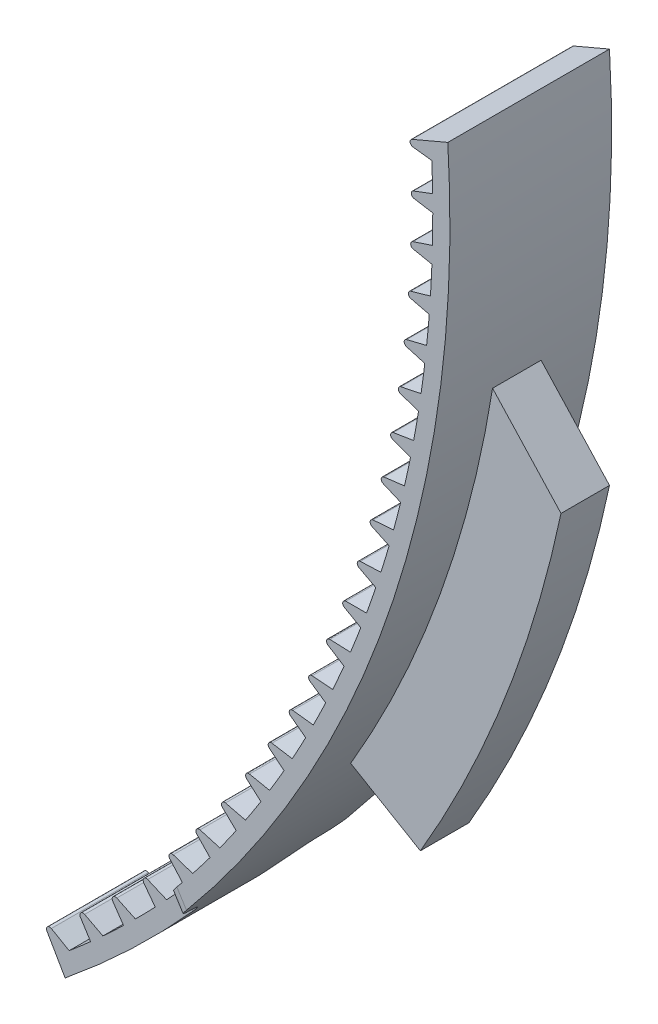
SolidWorks part; units mm, degrees
ref_plane "Plan de face" through (0, 0, 0) normal (0, 0, 1) x (1, 0, 0)
ref_plane "Plan de dessus" through (0, 0, 0) normal (0, 1, 0) x (1, 0, 0)
ref_plane "Plan de droite" through (0, 0, 0) normal (1, 0, 0) x (0, 0, -1)
sketch "Esquisse1" plane through (0, 0, 0) normal (0, 0, 1) x (1, 0, 0)
  line L0 (-30.5715, 0) -> (-35.8869, 0) construction
  line L1 (-30.5715, 0) -> (-32.0715, 2.5981)
  line L2 (-32.0715, 2.5981) -> (-30.323, 1.5885)
  line L3 (-28.998, 2.7351) -> (-30.0249, 4.3591)
  line L4 (-30.0249, 4.3591) -> (-28.2371, 3.4208)
  line L5 (-26.9594, 4.6198) -> (-28.0509, 6.2012)
  line L6 (-28.0509, 6.2012) -> (-26.2268, 5.3356)
  line L7 (-24.9984, 6.5851) -> (-26.1527, 8.1212)
  line L8 (-26.1527, 8.1212) -> (-24.2952, 7.3298)
  line L9 (-23.1181, 8.6277) -> (-24.3333, 10.1161)
  line L10 (-24.3333, 10.1161) -> (-22.4454, 9.4002)
  line L11 (-21.3215, 10.7444) -> (-22.5957, 12.1827)
  line L12 (-22.5957, 12.1827) -> (-20.6805, 11.5433)
  line L13 (-19.6117, 12.9318) -> (-20.9428, 14.3175)
  line L14 (-20.9428, 14.3175) -> (-19.0034, 13.7558)
  line L15 (-17.9913, 15.1861) -> (-19.3771, 16.5172)
  line L16 (-19.3771, 16.5172) -> (-17.4167, 16.034)
  line L17 (-16.463, 17.5039) -> (-17.9013, 18.7781)
  line L18 (-17.9013, 18.7781) -> (-15.923, 18.3742)
  line L19 (-15.0293, 19.8814) -> (-16.5177, 21.0966)
  line L20 (-16.5177, 21.0966) -> (-14.5248, 20.7728)
  line L21 (-13.6925, 22.3147) -> (-15.2286, 23.469)
  line L22 (-15.2286, 23.469) -> (-13.2242, 23.2256)
  line L23 (-12.4547, 24.7998) -> (-14.036, 25.8913)
  line L24 (-14.036, 25.8913) -> (-12.0235, 25.7289)
  line L25 (-11.318, 27.3327) -> (-12.942, 28.3597)
  line L26 (-12.942, 28.3597) -> (-10.9246, 28.2784)
  line L27 (-10.2842, 29.9094) -> (-11.9483, 30.8701)
  line L28 (-11.9483, 30.8701) -> (-9.9292, 30.8701)
  line L29 (-9.355, 32.5256) -> (-11.0564, 33.4186)
  line L30 (-11.0564, 33.4186) -> (-9.039, 33.4999)
  line L31 (-8.5319, 35.1771) -> (-10.2679, 36.0008)
  line L32 (-10.2679, 36.0008) -> (-8.2553, 36.1633)
  line L33 (-7.8163, 37.8596) -> (-9.584, 38.6127)
  line L34 (-9.584, 38.6127) -> (-7.5796, 38.8561)
  line L35 (-7.2092, 40.5687) -> (-9.0058, 41.2501)
  line L36 (-9.0058, 41.2501) -> (-7.0128, 41.574)
  line L37 (-6.7117, 43.3001) -> (-8.5343, 43.9086)
  line L38 (-8.5343, 43.9086) -> (-6.556, 44.3124)
  line L39 (-6.3246, 46.0493) -> (-8.1702, 46.5839)
  line L40 (-8.1702, 46.5839) -> (-6.2098, 47.0671)
  line L41 (-6.0485, 48.8118) -> (-7.9141, 49.2717)
  line L42 (-7.9141, 49.2717) -> (-5.9747, 49.8334)
  line L43 (-5.8838, 51.5833) -> (-7.7665, 51.9676)
  line L44 (-7.7665, 51.9676) -> (-5.8513, 52.607)
  line L45 (-5.8309, 54.3591) -> (-7.7275, 54.6673)
  line L46 (-7.7275, 54.6673) -> (-5.8396, 55.3833)
  line L47 (-5.8898, 57.1348) -> (-7.7973, 57.3664)
  line L48 (-7.7973, 57.3664) -> (-4.8995, 58.601)
  line L55 (-5.657, 65.4161) -> (-8.657, 65.4161) [skipped]
  line L56 (-8.657, 65.4161) -> (-5.9292, 66.991) [skipped]
  line L57 (-8.2624, 62.7451) -> (-5.4734, 64.2089) [skipped]
  line L58 (-5.2649, 62.6243) -> (-8.2624, 62.7451) [skipped]
  line L59 (-7.9757, 60.0604) -> (-5.13, 61.4107) [skipped]
  line L60 (-4.9854, 59.819) -> (-7.9757, 60.0604) [skipped]
  arc A0 (-30.323, 1.5885) -> (-28.998, 2.7351) centre (-74.7663, 54.2846) ccw
  arc A1 (-30.5715, 0) -> (-5, 60) centre (-74.7663, 54.2846) ccw
  arc A2 (-5.8396, 55.3833) -> (-5.8898, 57.1348) centre (-74.7663, 54.2846) ccw
  arc A3 (-5.8513, 52.607) -> (-5.8309, 54.3591) centre (-74.7663, 54.2846) ccw
  arc A4 (-28.2371, 3.4208) -> (-26.9594, 4.6198) centre (-74.7663, 54.2846) ccw
  arc A5 (-26.2268, 5.3356) -> (-24.9984, 6.5851) centre (-74.7663, 54.2846) ccw
  arc A6 (-24.2952, 7.3298) -> (-23.1181, 8.6277) centre (-74.7663, 54.2846) ccw
  arc A7 (-22.4454, 9.4002) -> (-21.3215, 10.7444) centre (-74.7663, 54.2846) ccw
  arc A8 (-20.6805, 11.5433) -> (-19.6117, 12.9318) centre (-74.7663, 54.2846) ccw
  arc A9 (-19.0034, 13.7558) -> (-17.9913, 15.1861) centre (-74.7663, 54.2846) ccw
  arc A10 (-17.4167, 16.034) -> (-16.463, 17.5039) centre (-74.7663, 54.2846) ccw
  arc A11 (-15.923, 18.3742) -> (-15.0293, 19.8814) centre (-74.7663, 54.2846) ccw
  arc A12 (-13.2242, 23.2256) -> (-12.4547, 24.7998) centre (-74.7663, 54.2846) ccw
  arc A13 (-12.0235, 25.7289) -> (-11.318, 27.3327) centre (-74.7663, 54.2846) ccw
  arc A14 (-10.9246, 28.2784) -> (-10.2842, 29.9094) centre (-74.7663, 54.2846) ccw
  arc A15 (-9.9292, 30.8701) -> (-9.355, 32.5256) centre (-74.7663, 54.2846) ccw
  arc A16 (-5.9747, 49.8334) -> (-5.8838, 51.5833) centre (-74.7663, 54.2846) ccw
  arc A17 (-6.2098, 47.0671) -> (-6.0485, 48.8118) centre (-74.7663, 54.2846) ccw
  arc A18 (-14.5248, 20.7728) -> (-13.6925, 22.3147) centre (-74.7663, 54.2846) ccw
  arc A19 (-9.039, 33.4999) -> (-8.5319, 35.1771) centre (-74.7663, 54.2846) ccw
  arc A20 (-8.2553, 36.1633) -> (-7.8163, 37.8596) centre (-74.7663, 54.2846) ccw
  arc A21 (-7.0128, 41.574) -> (-6.7117, 43.3001) centre (-74.7663, 54.2846) ccw
  arc A22 (-7.5796, 38.8561) -> (-7.2092, 40.5687) centre (-74.7663, 54.2846) ccw
  arc A23 (-6.556, 44.3124) -> (-6.3246, 46.0493) centre (-74.7663, 54.2846) ccw
  point P90 (-74.7663, 54.2846)
  dimension "D1" = 60
  dimension "D2" = 3
  dimension "D3" = 30
  dimension "D4" = 27
extrude "Boss.-Extru.1" add sketch "Esquisse1" against normal blind 10 contours A23 L38 L37 A21 L36 L35 A22 L34 L33 A20 L32 L31 A19 L30 L29 A15 L28 L27 A14 L26 L25 A13 L24 L23 A12 L22 L21 A18 L20 L19 A11 L18 L17 A10 L16 L15 A9 L14 L13 A8 L12 L11 A7 L10 L9 A6 L8 L7 A5 L6 L5 region at (-30.7616, 1.6223, 0)
fillet "Congé1" radius 0.2 1 edges at (-32.0715, 2.5981, -5)
fillet "Congé2" radius 0.2 23 edges at (-7.7973, 57.3664, -5) (-7.7275, 54.6673, -5) (-7.7665, 51.9676, -5) (-7.9141, 49.2717, -5) (-8.1702, 46.5839, -5) (-8.5343, 43.9086, -5) (-9.0058, 41.2501, -5) (-9.584, 38.6127, -5) (-11.0564, 33.4186, -5) (-10.2679, 36.0008, -5) (-11.9483, 30.8701, -5) (-12.942, 28.3597, -5) (-14.036, 25.8913, -5) (-15.2286, 23.469, -5) (-16.5177, 21.0966, -5) (-17.9013, 18.7781, -5) (-19.3771, 16.5172, -5) (-20.9428, 14.3175, -5) (-22.5957, 12.1827, -5) (-24.3333, 10.1161, -5) (-26.1527, 8.1212, -5) (-28.0509, 6.2012, -5) (-30.0249, 4.3591, -5)
sketch "Esquisse2" plane through (0, 0, 0) normal (0, 0, 1) x (1, 0, 0)
  line L0 (-10.0967, 16.2999) -> (-14.4765, 18.8724)
  line L1 (-16.2731, 10.6033) -> (-10.0967, 16.2999) construction
  line L2 (-5.6312, 43.3145) -> (-1.3981, 38.7248)
  line L3 (-5.6312, 43.3145) -> (-1.3981, 38.7248) construction
  arc A0 (-14.7909, 9.2519) -> (-0.2097, 46.1412) centre (-74.7663, 54.2846) ccw construction
  arc A1 (-30.5715, 0) -> (-4.8995, 58.601) centre (-74.7663, 54.2846) ccw construction
  arc A2 (-10.0967, 16.2999) -> (-1.3981, 38.7248) centre (-74.7663, 54.2846) ccw
  arc A3 (-14.408, 18.8322) -> (-5.6312, 43.3145) centre (-74.7663, 54.2846) ccw
extrude "Boss.-Extru.2" add sketch "Esquisse2" against normal blind 3 from offset 3.5 contours A3 L0 A2 L2 region at (-7.2238, 29.0551, 0) offset against normal yes
sketch "Esquisse3" plane through (-15.3271, 28.5268, 36.9109) normal (-0.5322, 0.8466, 0) x (-0.8466, -0.5322, 0)
  line L0 (26.9168, -38.9109) -> (17.3863, -38.9109)
  line L1 (29.3915, -38.9109) -> (23.9381, -38.9109) construction
  line L2 (28.6073, -41.9109) -> (16.8962, -41.9109) construction
  line L4 (28.0874, -36.9109) -> (-24.8326, -36.9109)
  line L5 (28.0874, -46.9109) -> (28.0874, -36.9109)
  line L6 (-24.8326, -46.9109) -> (28.0874, -46.9109)
  line L7 (-24.8326, -36.9109) -> (-24.8326, -46.9109)
  line L8 (28.0874, -36.9109) -> (15.0459, -36.9109)
  line L12 (26.9168, -44.9109) -> (17.3863, -44.9109)
  line L14 (28.0874, -46.9109) -> (15.0459, -46.9109)
  line L15 (26.9168, -38.9109) -> (28.0874, -38.9109)
  line L16 (28.0874, -46.9109) -> (28.0874, -36.9109) construction
  line L17 (28.0874, -38.9109) -> (28.0874, -36.9109)
  line L18 (26.9168, -44.9109) -> (28.0874, -44.9109)
  line L19 (28.0874, -44.9109) -> (28.0874, -46.9109)
  arc A0 (17.3863, -38.9109) -> (16.0513, -37.7711) centre (17.3863, -37.5591) cw
  arc A1 (16.0513, -37.7711) -> (15.0459, -36.9109) centre (15.0437, -37.931) ccw
  arc A2 (16.0513, -46.0506) -> (15.0459, -46.9109) centre (15.0437, -45.8907) cw
  arc A3 (17.3863, -44.9109) -> (16.0513, -46.0506) centre (17.3863, -46.2626) ccw
  spline S0 degree 3 poles (15.0459, -36.9109) (15.0761, -36.9116) (15.1362, -36.9131) (15.2256, -36.9253) (15.3135, -36.9448) (15.4281, -36.9813) (15.565, -37.0451) (15.7126, -37.1499) (15.8399, -37.2786) (15.941, -37.4286) (16.0164, -37.5938) (16.0397, -37.712) (16.0513, -37.7711) knots 0 0 0 0 0.062802 0.125108 0.187404 0.250175 0.375224 0.500064 0.625125 0.749923 0.87505 1 1 1 1 construction
  dimension "D1" = 0
extrude "Enlèv. mat.-Extru.1" cut sketch "Esquisse3" against normal through all contours A2 L14 L19 L18 L12 A3 | L8 A1 A0 L0 L15 L17
